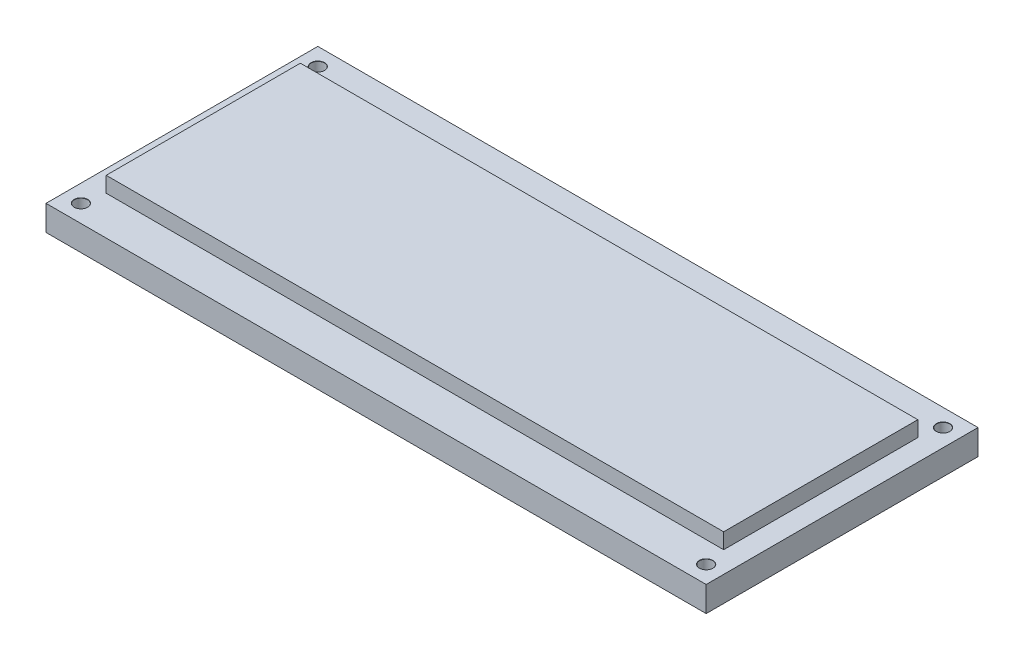
SolidWorks part; units mm, degrees
ref_plane "Front Plane" through (0, 0, 0) normal (0, 0, 1) x (1, 0, 0)
ref_plane "Top Plane" through (0, 0, 0) normal (0, 1, 0) x (1, 0, 0)
ref_plane "Right Plane" through (0, 0, 0) normal (1, 0, 0) x (0, 0, -1)
sketch "Sketch1" plane through (0, 0, 0) normal (0, 1, 0) x (1, 0, 0)
  line L1 (-85, 35) -> (85, 35)
  line L2 (-85, 35) -> (-85, -35)
  line L3 (-85, -35) -> (85, -35)
  line L4 (85, 35) -> (85, -35)
  line L5 (-85, 35) -> (85, -35) construction
  line L6 (-85, -35) -> (85, 35) construction
  point P0 (0, 0)
  dimension "D1" = 70
  dimension "D2" = 170
extrude "Boss-Extrude1" add sketch "Sketch1" along normal blind 6.5
sketch "Sketch2" plane through (0, 6.5, 0) normal (0, 1, 0) x (1, 0, 0)
  line L0 (85, 35) -> (-85, 35) construction
  line L1 (-79.5, -25) -> (79.5, -25)
  line L2 (-79.5, -25) -> (-79.5, 25)
  line L3 (-79.5, 25) -> (79.5, 25)
  line L4 (79.5, -25) -> (79.5, 25)
  line L5 (-79.5, -25) -> (79.5, 25) construction
  line L6 (-79.5, 25) -> (79.5, -25) construction
  line L7 (85, -35) -> (85, 35) construction
  point P0 (0, 0)
  dimension "D1" = 10
  dimension "D2" = 5.5
extrude "Boss-Extrude2" add sketch "Sketch2" along normal blind 4 contours L3 L4 L1 L2
hole_wizard "M3 Clearance Hole1" positions "Sketch3" profile "Sketch5" hole size "M3" standard "ISO" end condition through all
sketch "Sketch3" plane through (0, 6.5, 0) normal (0, 1, 0) x (1, 0, 0)
  line L23 (80.5, -30.5) -> (80.5, 30.5)
  line L24 (-80.5, -30.5) -> (80.5, -30.5)
  line L25 (-80.5, 30.5) -> (-80.5, -30.5)
  line L26 (80.5, 30.5) -> (-80.5, 30.5)
  line L27 (80.5, -30.5) -> (80.5, 30.5)
  line L28 (-80.5, -30.5) -> (80.5, -30.5)
  line L29 (-80.5, 30.5) -> (-80.5, -30.5)
  line L30 (80.5, 30.5) -> (-80.5, 30.5)
  point P46 (80.5, -30.5)
  point P47 (80.5, 30.5)
  point P48 (-80.5, -30.5)
  point P49 (-80.5, 30.5)
  dimension "D1" = 4.5
sketch "Sketch5" plane through (80.5, 6.5, 30.5) normal (1, 0, 0) x (0, 0, 1)
  line L0 (0, 0) -> (0, 6.5)
  line L1 (0, 6.5) -> (1.7, 6.5)
  line L2 (1.7, 6.5) -> (1.7, 0.05)
  line L3 (1.7, 0.05) -> (1.75, 0)
  line L5 (1.75, 0) -> (0, 0)
  line L6 (-1.7, 0.05) -> (-1.75, 0) construction
  line L11 (0, -6.35) -> (0, 107.95) construction
  dimension "Thru Hole Dia." = 3.4
  dimension "Thru Hole Depth" = 6.5
  dimension "Near C'Sink Dia." = 3.5
  dimension "Near C'Sink Angle" = 90
